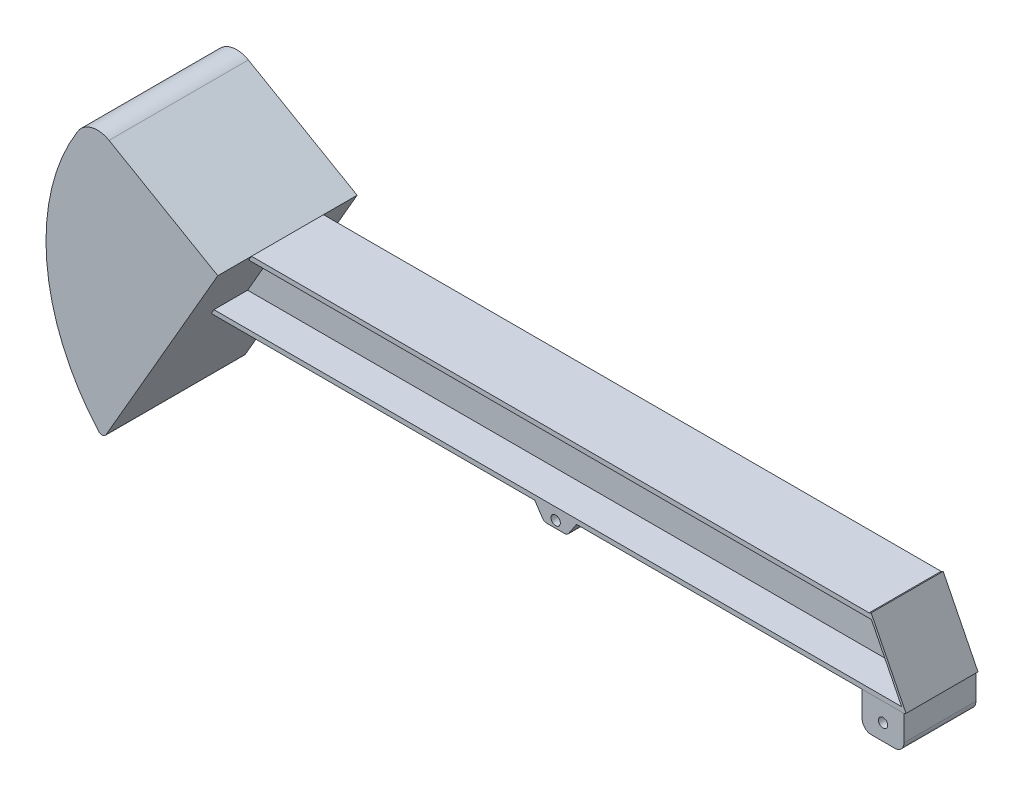
SolidWorks part; units mm, degrees
ref_plane "Front Plane" through (0, 0, 0) normal (0, 0, 1) x (1, 0, 0)
ref_plane "Top Plane" through (0, 0, 0) normal (0, 1, 0) x (1, 0, 0)
ref_plane "Right Plane" through (0, 0, 0) normal (1, 0, 0) x (0, 0, -1)
sketch "Sketch1" plane through (0, 0, 0) normal (0, 0, 1) x (1, 0, 0)
  line L0 (-45, 0) -> (45, 0)
  line L1 (-45, 0) -> (-25, -30)
  line L2 (-25, -30) -> (25, -30)
  line L3 (25, -30) -> (45, 0)
  line L4 (0, 0) -> (0, -30) construction
  dimension "D1" = 90
  dimension "D2" = 50
  dimension "D3" = 30
extrude "Boss-Extrude1" add sketch "Sketch1" along normal mid plane 155
fillet "Fillet1" radius 10 2 edges at (25, -30, 0) (-25, -30, 0)
sketch "Sketch2" plane through (0, 0, 77.5) normal (0, 0, 1) x (1, 0, 0)
  circle A0 centre (0, -15) radius 10
  dimension "D1" = 20
  dimension "D2" = 15
extrude "Cut-Extrude1" cut sketch "Sketch2" against normal through all
sketch "Sketch3" plane through (0, 0, 0) normal (1, 0, 0) x (0, 0, -1)
  line L0 (-77.5, 0) -> (77.5, 0)
  line L1 (77.5, 0) -> (77.5, 10)
  line L2 (77.5, 10) -> (5, 10)
  line L3 (5, 10) -> (5, 140)
  line L4 (5, 140) -> (77.5, 140)
  line L5 (77.5, 140) -> (77.5, 150)
  line L6 (77.5, 150) -> (-77.5, 150)
  line L7 (-77.5, 150) -> (-77.5, 140)
  line L8 (-77.5, 140) -> (-5, 140)
  line L9 (-5, 140) -> (-5, 10)
  line L10 (-5, 10) -> (-77.5, 10)
  line L11 (-77.5, 10) -> (-77.5, 0)
  point P14 (77.5, 145)
  dimension "D1" = 10
  dimension "D2" = 150
  dimension "D3" = 5
  dimension "D4" = 5
extrude "Boss-Extrude2" add sketch "Sketch3" along normal blind 750 and the other way blind 750
sketch "Sketch4" plane through (0, 0, 0) normal (0, 0, 1) x (1, 0, 0)
  line L0 (-655, 150) -> (-928.798, 308.0773)
  line L1 (-655, 150) -> (-902.4761, -278.6412)
  line L2 (-750, 150) -> (750, 150) construction
  line L3 (-750, 140) -> (-750, 10) construction
  arc A0 (-928.798, 308.0773) -> (-902.4761, -278.6412) centre (-575, 30) ccw
  dimension "D4" = 450
  dimension "D1" = 95
  dimension "D2" = 30
  dimension "D3" = 60
  dimension "D5" = 575
  dimension "D6" = 30
extrude "Boss-Extrude3" add sketch "Sketch4" along normal mid plane 300
fillet "Fillet2" radius 50 1 edges at (-928.798, 308.0773, 0)
fillet "Fillet3" radius 10 1 edges at (-902.4761, -278.6412, 0)
sketch "Sketch5" plane through (0, 0, 5) normal (0, 0, 1) x (1, 0, 0)
  line L0 (750, 0) -> (675, 150)
  line L1 (-655, 150) -> (750, 150) construction
  line L2 (675, 150) -> (750, 150)
  line L3 (750, 150) -> (750, 0)
  dimension "D1" = 75
extrude "Cut-Extrude2" cut sketch "Sketch5" against normal mid plane 300
sketch "Sketch6" plane through (600, 300, 0) normal (0.8944, 0.4472, 0) x (0, 0, -1)
  line L1 (-77.5, -167.7051) -> (77.5, -167.7051)
  line L2 (-77.5, -167.7051) -> (-77.5, -335.4102)
  line L3 (-77.5, -335.4102) -> (77.5, -335.4102)
  line L4 (77.5, -167.7051) -> (77.5, -335.4102)
extrude "Boss-Extrude4" add sketch "Sketch6" along normal blind 5
sketch "Sketch7" plane through (0, 0, 77.5) normal (0, 0, 1) x (1, 0, 0)
  line L0 (750, 0) -> (660, 0)
  line L1 (45, 0) -> (750, 0) construction
  line L2 (660, 0) -> (660, -75)
  line L3 (660, -75) -> (750, -75)
  line L4 (750, -75) -> (750, 0)
  dimension "D1" = 90
  dimension "D2" = 75
extrude "Boss-Extrude5" add sketch "Sketch7" against normal up to surface (155 mm away) separate body up to face at (93.1712, 40.0807, -77.5)
fillet "Fillet4" radius 20 2 edges at (660, -75, 0) (750, -75, 0)
sketch "Sketch8" plane through (0, 0, 77.5) normal (0, 0, 1) x (1, 0, 0)
  line L0 (680, -75) -> (730, -75) construction
  line L1 (660, 0) -> (660, -55) construction
  circle A0 centre (705, -40) radius 10
  dimension "D1" = 20
  dimension "D2" = 35
  dimension "D3" = 45
extrude "Cut-Extrude3" cut sketch "Sketch8" against normal through all
